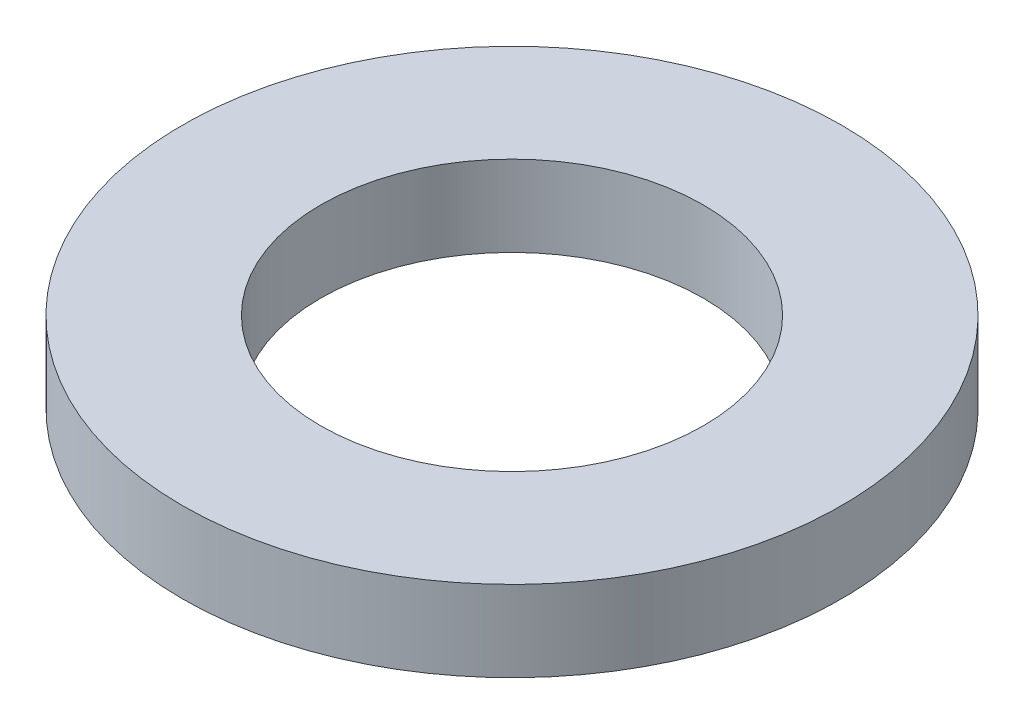
SolidWorks part; units mm, degrees
ref_plane "Front Plane" through (0, 0, 0) normal (0, 0, 1) x (1, 0, 0)
ref_plane "Top Plane" through (0, 0, 0) normal (0, 1, 0) x (1, 0, 0)
ref_plane "Right Plane" through (0, 0, 0) normal (1, 0, 0) x (0, 0, -1)
sketch "Sketch1" plane through (0, 0, 0) normal (0, 1, 0) x (1, 0, 0)
  circle A0 centre (0, 0) radius 77.5
  dimension "FLANGE_OD" = 155
extrude "Boss-Extrude1" add sketch "Sketch1" along normal blind 19
sketch "Sketch2" plane through (0, 0, 0) normal (0, 1, 0) x (1, 0, 0)
  circle A0 centre (0, 0) radius 45
  dimension "BORE_D" = 90
extrude "Cut-Extrude1" cut sketch "Sketch2" along normal through all
sketch "Sketch3" plane through (0, 19, 0) normal (0, 1, 0) x (1, 0, 0)
  circle A0 centre (0, 0) radius 35.8256 construction
  circle A1 centre (-35.8256, 0) radius 2.564
  dimension "BOLT_D" = 5.1281
  dimension "BOLT_PCD" = 71.6512
extrude "Cut-Extrude2" cut sketch "Sketch3" against normal blind 17.3829 rebuild error yes
pattern_circular "CirPattern1" count 8 over 360 rebuild error yes
